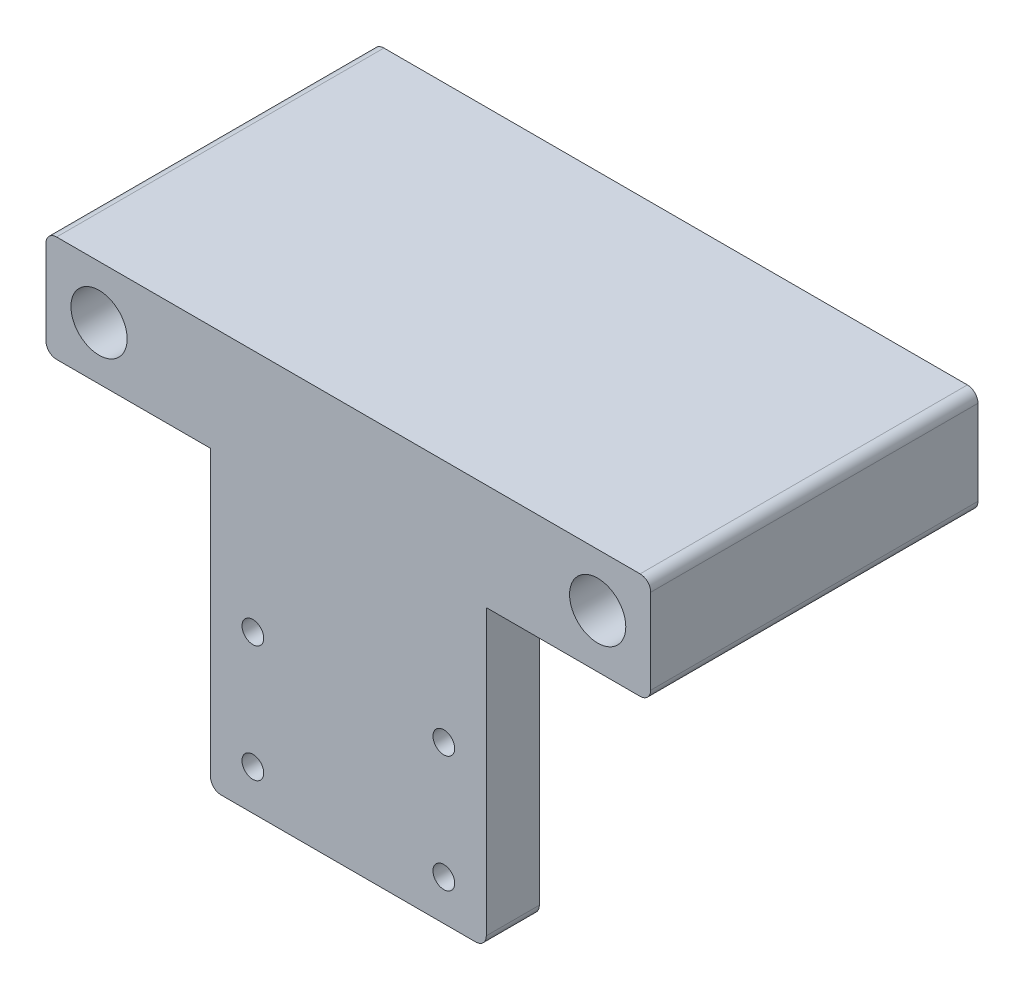
SolidWorks part; units mm, degrees
material "ABS"
ref_plane "Front Plane" through (0, 0, 0) normal (0, 0, 1) x (1, 0, 0)
ref_plane "Top Plane" through (0, 0, 0) normal (0, 1, 0) x (1, 0, 0)
ref_plane "Right Plane" through (0, 0, 0) normal (1, 0, 0) x (0, 0, -1)
sketch "Body Sketch" plane through (0, 0, 0) normal (0, 0, 1) x (1, 0, 0)
  line L0 (0, -5.5) -> (0, -7.3) construction
  line L1 (-11, 20.7) -> (11, 20.7) construction
  line L2 (-11, 20.7) -> (-11, -7.3) construction
  line L3 (-11, -7.3) -> (11, -7.3) construction
  line L4 (11, 20.7) -> (11, -7.3) construction
  line L5 (-11, 20.7) -> (11, -7.3) construction
  line L6 (-11, -7.3) -> (11, 20.7) construction
  line L7 (-9, 5.5) -> (9, 5.5) construction
  line L8 (-9, 5.5) -> (-9, -5.5) construction
  line L9 (-9, -5.5) -> (9, -5.5) construction
  line L10 (9, 5.5) -> (9, -5.5) construction
  line L11 (0, 5.5) -> (0, -5.5) construction
  line L12 (-9, 0) -> (9, 0) construction
  line L13 (-28.5, 18.5) -> (-13, 18.5)
  line L18 (-13, 18.5) -> (-13, -9.3)
  line L19 (-13, -9.3) -> (13, -9.3)
  line L20 (-28.5, -28.5) -> (28.5, -28.5) construction
  line L21 (-28.5, -28.5) -> (-28.5, 28.5)
  line L22 (-28.5, 28.5) -> (28.5, 28.5)
  line L23 (28.5, -28.5) -> (28.5, 28.5)
  line L24 (-28.5, -28.5) -> (28.5, 28.5) construction
  line L25 (-28.5, 28.5) -> (28.5, -28.5) construction
  line L26 (13, -9.3) -> (13, 18.5)
  line L27 (13, 18.5) -> (28.5, 18.5)
  line L30 (-23.5, 23.5) -> (23.5, 23.5) construction
  line L31 (-23.5, 23.5) -> (-23.5, -23.5) construction
  line L32 (-23.5, -23.5) -> (23.5, -23.5) construction
  line L33 (23.5, 23.5) -> (23.5, -23.5) construction
  line L34 (-13, 18.5) -> (13, 18.5)
  circle A0 centre (9, 5.5) radius 1.3 construction
  circle A1 centre (-9, -5.5) radius 1.3 construction
  circle A2 centre (-23.5, 23.5) radius 5 construction
  circle A3 centre (23.5, 23.5) radius 5 construction
  circle A4 centre (0, 0) radius 4 construction
  point P16 (0, 0)
  point P17 (0, 0)
  point P24 (0, 0)
  point P44 (0, -9.3)
  dimension "D1" = 2.6
  dimension "Clearance Hole Diameter" = 10
  dimension "D11" = 8
  dimension "PCB Width" = 22
  dimension "PCB Height" = 28
  dimension "D2" = 11
  dimension "D3" = 18
  dimension "D4" = 1.8
  dimension "D5" = 57
  dimension "D12" = 47
  dimension "Overlap" = 2
  dimension "LateralOverlap" = 2
extrude "PCB Mount" add sketch "Body Sketch" along normal blind 5 contours L18 L27 | L27 region at (0, 23.5, 0) region at (0, 4.6, 0)
extrude "Stepper Offset Mount" add sketch "Body Sketch<6>" against normal blind 25.85 contours L13 L34 L27 L23 L22 L21 region at (0, 23.5, 0)
sketch "Body Sketch<6>" plane through (0, 0, 0) normal (0, 0, 1) x (1, 0, 0) same geometry as "Body Sketch"
hole_wizard "M5 Clearance Hole1" positions "Sketch3" profile "Sketch5" hole size "M5" standard "ANSI Metric" end condition through all
sketch "Sketch3" plane through (0, 0, 5) normal (0, 0, 1) x (1, 0, 0)
  point P0 (-23.5, 23.5)
  point P3 (23.5, 23.5)
sketch "Sketch5" plane through (-23.5, 23.5, 5) normal (1, 0, 0) x (0, -1, 0)
  line L0 (0, 0) -> (0, 30.85)
  line L1 (0, 30.85) -> (2.65, 30.85)
  line L2 (2.65, 30.85) -> (2.65, 0)
  line L5 (2.65, 0) -> (0, 0)
  line L11 (0, -6.35) -> (0, 107.95) construction
  dimension "Thru Hole Dia." = 5.3
  dimension "Thru Hole Depth" = 30.85
hole_wizard "Tap Drill for M2.5x0.45 Tap1" positions "Sketch6" profile "Sketch7" hole size "M2.5x0.45" standard "ANSI Metric" end condition through all
sketch "Sketch6" plane through (0, 0, 5) normal (0, 0, 1) x (1, 0, 0)
  point P0 (-9, 5.5)
  point P3 (-9, -5.5)
  point P6 (9, -5.5)
  point P9 (9, 5.5)
sketch "Sketch7" plane through (-9, 5.5, 5) normal (1, 0, 0) x (0, -1, 0)
  line L0 (0, 0) -> (0, 30.85)
  line L1 (0, 30.85) -> (1.025, 30.85)
  line L2 (1.025, 30.85) -> (1.025, 0)
  line L5 (1.025, 0) -> (0, 0)
  line L11 (0, -6.35) -> (0, 107.95) construction
  dimension "Thru Hole Dia." = 2.05
  dimension "Thru Hole Depth" = 30.85
fillet "Fillet1" radius 1 4 edges at (-28.5, 18.5, -10.425) (-28.5, 28.5, -10.425) (28.5, 18.5, -10.425) (28.5, 28.5, -10.425)
fillet "Fillet2" radius 1 2 edges at (13, -9.3, 2.5) (-13, -9.3, 2.5)
equation "\"D5@Body Sketch\" = 57mm"
equation "\"Clearance Hole Diameter@Body Sketch\" = \"M5_ClearanceDiameter\""
equation "\"ExtrusionStandard\"= 20mm'Size of extrusion used for framing"
equation "\"BaseExtrusionFrameWidth\"= 60mm'Width of the central aluminum extrusion"
equation "\"BaseExtrusionFrameHeight\"= 20mm'Height of the central aluminum extrusion"
equation "\"PlateThickness\"= 15mm'Thickness of the the front and back framing plates"
equation "\"RailHeight\"= 13mm'Total height of the carriage and rail component"
equation "\"WallThickness\"= 3mm'Standard wall thickness"
equation "\"ShaftDiameter\"= 20mm'Outside Diameter of the main yoke shaft"
equation "\"ShaftClearance\"= 1mm'Clearance/gap between the main yoke and non-bearing elements"
equation "\"PlainBearingBoltCircleDiameter\"= ( \"WallThickness\" + \"M3_ClearanceDiameter\" / 2 ) * 2 + \"PlainBearingOD\"'Bolt circle diameter for the plain bearing retainer/mount"
equation "\"PlainBearingBoltcount\"= 5'Number of bolts used in the plain bearing/mount"
equation "\"LeadScrewDiameter\"= 6.35mm'OD of the leadsrew used on the Y axis"
equation "\"LeadScrewHeight\"= 10mm'Height of the center of the Lead screw from bottom of gantry extrusion"
equation "\"LeadScrewNut_FlangeOD\"= 25mm'OD of the lead screw nut flange"
equation "\"LeadScrewNut_BoltCircleDiameter\"= 19mm'Bolt circle diameter needed to mount the leadscrew nut"
equation "\"LeadScrewNut_BoltCount\"= 6'Number of bolts required to mount the leadscrew nut to gantry."
equation "\"X_BeltPitch\"= 2mm'Pitch of the timing belt used on the X axis/main shaft."
equation "\"X_Drive_Teeth\"= 20'Number of teeth used on the X/Main stepper motor pulley"
equation "\"X_Shaft_Teeth\"= 60'Number of teeth on the X/Main shaft pulley"
equation "\"X_Drive_PD\"= ( \"X_Drive_Teeth\" * \"X_BeltPitch\" ) / PI'Pitch Diameter of the X/main motor pulley"
equation "\"X_Shaft_PD\"= ( \"X_Shaft_Teeth\" * \"X_BeltPitch\" ) / PI'Pitch Diameter of the X/main shaft pulley"
equation "\"X_CenterDistance\" = 60mm'Distance between the main shaft and motor pulley centers"
equation "\"GantryLength\"= 150mm'Length of the gantry extrusion/plate"
equation "\"X_MotorPlateThickness\"= 15mm'Thickness of the plate used to hold the X/main motor"
equation "\"X_MotorPlateLength\"= \"X_MotorPlateThickness\" + \"ExtrusionStandard\" * 2'FIXME"
equation "\"X_BeltWidth\" = 9mm'Width of the timing belt used on the X/Main shaft rotary drive"
equation "\"X_PillowLength\"= ( \"WallThickness\" * 4 ) + \"X_RearCollarThickness\" + ( \"X_ThrustBearingThickness\" * 2 ) + \"X_ShaftRotaryBearingThickness\"'Total length of the pillow block used to hold the main shaft"
equation "\"ShaftLength\"= 400mm'Length of the main shaft."
equation "\"PlainBearingOD\"= 31.8mm'OD of the Plain Bearing housing"
equation "\"Y_Drive_Length\"= \"ShaftLength\"'duplicate"
equation "\"Y_Drive_Diameter\"= \"LeadScrewDiameter\"'duplicate"
equation "\"Y_Drive_ThrustBearingOD\"= .5625in'OD of the thrust bearings used to support the leadscrew/Y drive"
equation "\"Y_Drive_ThrustBearingThickness\"= .193in'Thickness of the thrust bearings used to support the leadscrew/Y drive"
equation "\"Y_Drive_ShaftCollarOD\"= .6875in'OD of the collar used to constrain the leadscrew/Y drive"
equation "\"Y_Drive_ShaftCollarThickness\"= .3125in'Thickness of the collar used to constrain the leadscrew/Y drive"
equation "\"Y_Drive_ShaftCollarClearance\"= .375in / 2'Amount of radial clearance needed around the leadscrew/Y shaft collar"
equation "\"calc_Y_Drive_BearingLargestDiameter\"= IIF ( \"Y_Drive_ThrustBearingOD\" > \"Y_Drive_ShaftCollarOD\" , \"Y_Drive_ThrustBearingOD\" , \"Y_Drive_ShaftCollarOD\" )'FIXME - calculated diameter needed for Y drive pillow - needs to account for collar clearance."
equation "\"Y_Drive_BearingBoltCircleDiameter\"= \"calc_Y_Drive_BearingLargestDiameter\" + ( \"Y_Drive_ShaftCollarClearance\" * 2 ) + ( \"WallThickness\" * 2 ) + 2 * 10mm'FIXME - unused?"
equation "\"M3_ClearanceDiameter\"= 8mm'Keepout diameter for M3 holes"
equation "\"M5_ClearanceDiameter\"= 10mm'Keepout Diameter for M5 holes"
equation "\"Y_Drive_CenterDistance\"= 60mm'Center Distance between Y motor drive and leadscrew pulley"
equation "\"Y_Drive_Teeth\"= 20'Number of teeth on the Y/linear stepper pulley"
equation "\"Y_Drive_ShaftTeeth\"= 60'Number of teeth on the Y/linear leadscrew pulley"
equation "\"Y_Drive_BeltWidth\"= 9mm'Width of the belt used on the Y/linear drive"
equation "\"Y_Drive_BeltPitch\"= 2mm'Pitch of the timing belt used on the Y/linear drive"
equation "\"Y_Drive_PD\"= ( \"Y_Drive_Teeth\" * \"Y_Drive_BeltPitch\" ) / PI'Pitch Diameter of the stepper pulley for the Y/linear drive"
equation "\"Y_Drive_ShaftPD\"= ( \"Y_Drive_ShaftTeeth\" * \"Y_Drive_BeltPitch\" ) / PI'Pitch diameter of the pulley on the Y/linear leadscrew"
equation "\"PlainBearingLength\"= 44.8mm'Length of the plain bearing housing"
equation "\"Y_Drive_ShaftBearingThickness\"= .196in'Thickness of the radial bearing used to support the Y leadscrew"
equation "\"Y_Drive_ShaftBearingOD\"= .625in'OD of the radial bearing used to support the Y leadscrew"
equation "\"EncoderMount_BoltWidth\"= 80mm"
equation "\"EncoderMount_BoltRowCount\" = 1"
equation "\"EncoderMount_BoltRowDistance\"= 20mm"
equation "\"EncoderMount_Offset\"= 10mm"
equation "\"Y_Drive_StepperShaftLength\"= 21mm"
equation "\"X_StepperShaftLength\" = 21mm"
equation "\"Y_DriveStepperShaftDiameter\"= 6.35mm"
equation "\"X_StepperShaftDiameter\"= 6.35mm"
equation "\"X_ThrustBearingOD\"= 35mm'OD of the thrust bearing used on the main shaft"
equation "\"X_ThrustBearingID\"= 20mm'ID of the thrust bearing used on the main shaft"
equation "\"X_ThrustBearingThickness\"= 10mm'Thickness of the thrust bearing used on the main shaft"
equation "\"X_RearCollarOD\"= 32mm'OD of the shaft collar of the main shaft"
equation "\"X_RearCollarID\"= 20mm'ID of the shaft collar of the main shaft"
equation "\"X_RearCollarThickness\"= 8mm'Thickness of the collar along the main shaft"
equation "\"X_ShaftRotaryBearingThickness\"= 9mm'Thickness of the radial bearing used on the main shaft"
equation "\"X_ShaftRotaryBearingOD\"= 37mm'OD of the radial bearing used on the main shaft"
equation "\"Pillow_BaseClearance\"= 6mm + \"WallThickness\"'Pillow block base needed to internally mount screws"
equation "\"X_PillowHeight\"= \"Pillow_BaseClearance\" + \"calc_X_PillowRadius\"'Height of the main shaft pillow block base, as measured from the top of the gantry surface"
equation "\"calc_X_PillowRadius\"= IIF ( ( \"X_ThrustBearingOD\" / 2 ) > ( \"X_RearCollarOD\" / 2 * 1.5 ) , \"X_ThrustBearingOD\" / 2 , ( \"X_RearCollarOD\" / 2 ) * 1.5 ) + ( \"WallThickness\" )'Minimum Radius needed for X/main shaft pillow block elements."
equation "\"calc_Y_PillowRadius\"= IIF ( \"Y_Drive_ThrustBearingOD\" / 2 > ( \"Y_Drive_ShaftCollarOD\" / 2 * 1.5 ) , \"Y_Drive_ThrustBearingOD\" / 2 , ( \"Y_Drive_ShaftCollarOD\" / 2 ) * 1.5 )'Minimum radius needed for the Y/linear shaft pillow block elements"
equation "\"Y_PillowHeight\"= \"Pillow_BaseClearance\" + \"calc_Y_PillowRadius\"'Height of the Y/linear pillow block base"
equation "\"Assembly_MainShaftStickout\"= 50mm'Amount of stickout at maximum pitch down (yoke forward)"
equation "\"PCB_Thickness\"= 2.6mm"
